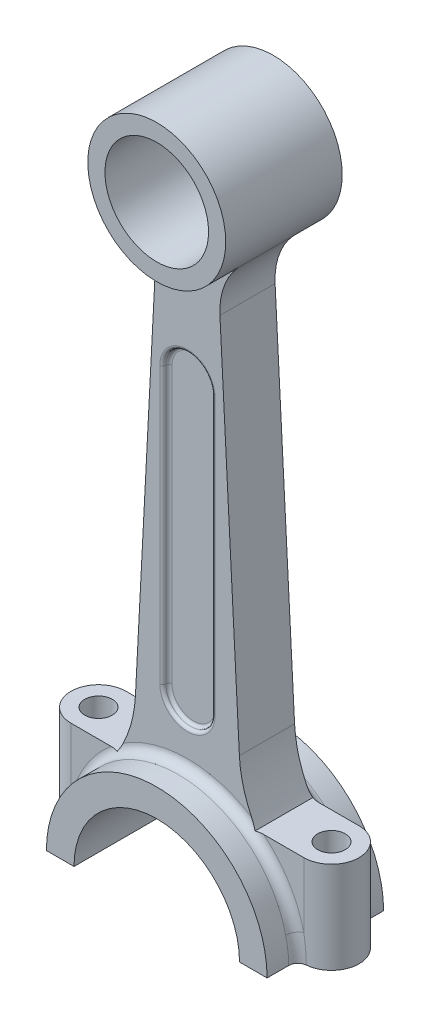
SolidWorks part; units mm, degrees
ref_plane "Front Plane" through (0, 0, 0) normal (0, 0, 1) x (1, 0, 0)
ref_plane "Top Plane" through (0, 0, 0) normal (0, 1, 0) x (1, 0, 0)
ref_plane "Right Plane" through (0, 0, 0) normal (1, 0, 0) x (0, 0, -1)
sketch "Sketch1" plane through (0, 0, 0) normal (0, 0, 1) x (1, 0, 0)
  line L0 (0, 0) -> (0, -201.2) construction
  line L1 (-10, -20.1556) -> (-17.8497, -169.9368)
  line L2 (10, -20.1556) -> (17.8497, -169.9368)
  line L3 (-36, -201.2) -> (-27, -201.2)
  line L4 (27, -201.2) -> (36, -201.2)
  circle A0 centre (0, 0) radius 22.5
  circle A1 centre (0, 0) radius 16.9
  arc A2 (27, -201.2) -> (-27, -201.2) centre (0, -201.2) ccw
  arc A3 (36, -201.2) -> (-36, -201.2) centre (0, -201.2) ccw
  dimension "D1" = 45
  dimension "D2" = 33.8
  dimension "D3" = 54
  dimension "D4" = 72
  dimension "D5" = 201.2
  dimension "D6" = 20
  dimension "D7" = 6
extrude "Boss-Extrude1" add sketch "Sketch1" along normal mid plane 38 contours A1 A0 | A3 A2 | L0 A3 L3 A2 region at (-4.9903, -21.2865, 0) region at (20.1899, -181.0101, 0) region at (-20.1899, -181.0101, 0)
extrude "Boss-Extrude2" add sketch "Sketch1<4>" along normal mid plane 18 contours L0 A0 L1 A3 | A0 L0 A3 L2 region at (7.1843, -100.8455, 0) region at (-7.1843, -100.8455, 0)
sketch "Sketch1<4>" plane through (0, 0, 0) normal (0, 0, 1) x (1, 0, 0) same geometry as "Sketch1"
sketch "Sketch2" plane through (0, 0, 9) normal (0, 0, 1) x (1, 0, 0)
  line L0 (0, 0) -> (0, -201.2) construction
  line L1 (0, -145.6) -> (0, -55.6) construction
  line L2 (-8, -145.6) -> (-8, -55.6)
  line L3 (8, -145.6) -> (8, -55.6)
  arc A0 (-8, -145.6) -> (8, -145.6) centre (0, -145.6) ccw
  arc A1 (8, -55.6) -> (-8, -55.6) centre (0, -55.6) ccw
  point P6 (0, -100.6)
  dimension "D2" = 8
  dimension "D1" = 90
extrude "Cut-Extrude1" cut sketch "Sketch2" against normal mid plane 4
mirror "Mirror1" about plane through (0, 0, 0) normal (0, 0, 1) of "Cut-Extrude1"
fillet "Fillet1" radius 1 16 edges at (0, -47.6, -7) (8, -100.6, -7) (0, -153.6, -7) (0, -153.6, -9) (8, -100.6, -9) (0, -47.6, -9) (0, -47.6, 9) (8, -100.6, 9) (0, -153.6, 9) (-8, -100.6, -7) (-8, -100.6, -9) (0, -47.6, 7) (8, -100.6, 7) (0, -153.6, 7) (-8, -100.6, 7) (-8, -100.6, 9)
fillet "Fillet2" radius 40 2 edges at (17.8497, -169.9368, 0) (-17.8497, -169.9368, 0)
fillet "Fillet3" radius 22.5 2 edges at (-10, -20.1556, 0) (10, -20.1556, 0)
ref_plane "Plane1" through (0, -171.2, 0) normal (0, -1, 0) x (-1, 0, 0)
sketch "Sketch3" plane through (0, -171.2, 0) normal (0, -1, 0) x (-1, 0, 0)
  line L0 (-38, 0) -> (38, 0) construction
  line L1 (-38, 9) -> (38, 9)
  line L2 (-38, -9) -> (38, -9)
  arc A0 (-38, 9) -> (-38, -9) centre (-38, 0) ccw
  arc A1 (38, -9) -> (38, 9) centre (38, 0) ccw
  point P2 (0, 0)
  dimension "D2" = 9
  dimension "D1" = 76
extrude "Boss-Extrude3" add sketch "Sketch3" along normal up to surface (30 mm away) up to face at (-31.5, -201.2, 0)
sketch "Sketch4" plane through (0, 0, 9) normal (0, 0, 1) x (1, 0, 0)
  line L1 (-27, -201.2) -> (27, -201.2)
  line L2 (-27, -201.2) -> (27, -201.2)
  arc A1 (27, -201.2) -> (-27, -201.2) centre (0, -201.2) ccw
  arc A2 (27, -201.2) -> (-27, -201.2) centre (0, -201.2) ccw
  dimension "D1" = 0
extrude "Cut-Extrude2" cut sketch "Sketch4" against normal through all
sketch "Sketch5" plane through (0, -171.2, 0) normal (0, 1, 0) x (1, 0, 0)
  circle A0 centre (-38, 0) radius 4.5
  circle A1 centre (38, 0) radius 4.5
  dimension "D1" = 9
  dimension "D2" = 9
extrude "Cut-Extrude3" cut sketch "Sketch5" against normal through all
fillet "Fillet4" radius 3 2 edges at (0, -165.2, -9) (0, -165.2, 9)
